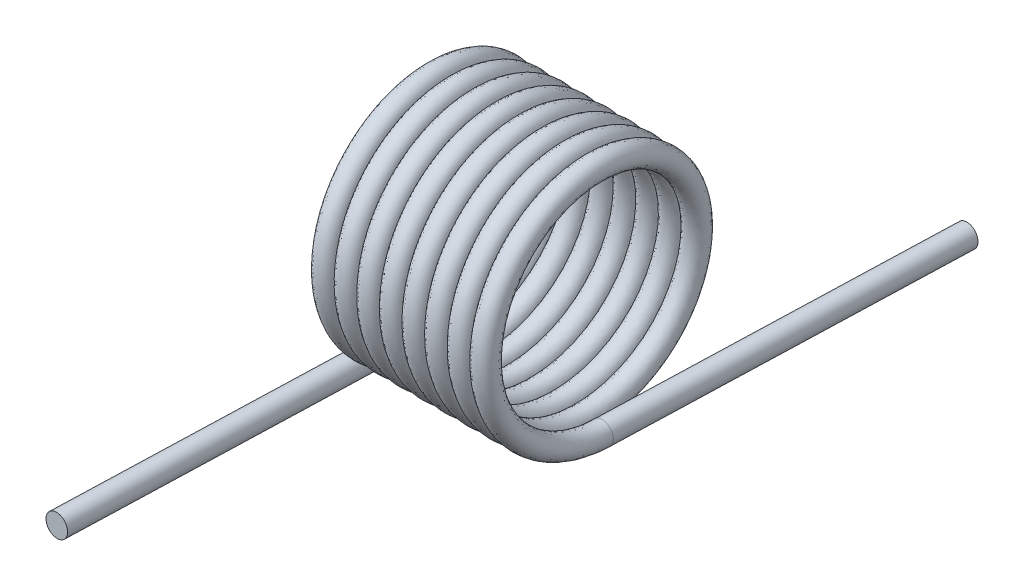
SolidWorks part; units mm, degrees
ref_plane "Front" through (0, 0, 0) normal (0, 0, 1) x (1, 0, 0)
ref_plane "Top" through (0, 0, 0) normal (0, 1, 0) x (1, 0, 0)
ref_plane "Right" through (0, 0, 0) normal (1, 0, 0) x (0, 0, -1)
sketch "Sketch1" plane through (0, 0, 0) normal (1, 0, 0) x (0, 0, -1)
  line L0 (0, 0) -> (0, -10.7696) construction
  line L1 (0, -10.7696) -> (0, -11.9761) construction
  line L2 (0, -11.9761) -> (0, -13.1826) construction
  circle A0 centre (0, 0) radius 10.7696 construction
  circle A1 centre (0, 0) radius 13.1826 construction
  circle A2 centre (0, 0) radius 11.9761
  circle A3 centre (0, -11.9761) radius 1.2065 construction
  circle A4 centre (0, 0) radius 8.7122 construction
curve "Helix/Spiral1" pitch 2.4384 height 19.5072 radius 11.9761 centre (0, 0, 0) axis (1, 0, 0) start towards (0, 0, -1)
ref_plane "Plane1" through (0, -11.9761, 0) normal (0.0324, 0, -0.9995) x (-0.9995, 0, -0.0324)
sketch "Sketch2" plane through (0, -11.9761, 0) normal (0.0324, 0, -0.9995) x (-0.9995, 0, -0.0324)
  circle A0 centre (0, 0) radius 1.2065
  dimension "D1" = 2.413
sweep "Sweep1" add profiles "Sketch2" path "Helix/Spiral1"
sketch "Sketch3" plane through (0, 0, 0) normal (-0.0324, 0, 0.9995) x (0.9995, 0, 0.0324)
  circle A1 centre (0, -11.9761) radius 1.2065
  circle A2 centre (0, -11.9761) radius 1.2065
  dimension "D1" = 0
extrude "Extrude1" add sketch "Sketch3" along normal blind 38.1
sketch "Sketch4" plane through (0.0205, 0, -0.6315) normal (0.0324, 0, -0.9995) x (-0.9958, -0.0856, -0.0323)
  circle A1 centre (-18.4002, -13.6011) radius 1.2065
  circle A2 centre (-18.4002, -13.6011) radius 1.2065
  dimension "D1" = 0
extrude "Extrude2" add sketch "Sketch4" along normal blind 38.1
sketch "Sketch5" plane through (0, 0, 0) normal (1, 0, 0) x (0, 0, -1)
  circle A0 centre (0, 0) radius 8.7122 construction
  circle A1 centre (0, 0) radius 8.7122
ref_axis "Axis1" through (24.5238, 0, 0) along (-1, 0, 0)
ref_plane "Plane2" through (0, -13.1826, 0) normal (0, -1, 0) x (-1, 0, 0)
ref_plane "Plane3" through (20.6926, 0, 0.6705) normal (0.9995, 0, 0.0324) x (0.0324, 0, -0.9995)
sketch "Sketch6" plane through (0, 0, 0) normal (1, 0, 0) x (0, 0, -1)
  circle A0 centre (0, 0) radius 11.9761
  dimension "D1" = 23.9522
equation "\"D4@Helix/Spiral1\"=\"Wire Dia@Sketch1\"+.001"
equation "\"D1@Sketch2\"=\"Wire Dia@Sketch1\""
equation "\"D1@Extrude2\"=\"Leg Length@Extrude1\""
